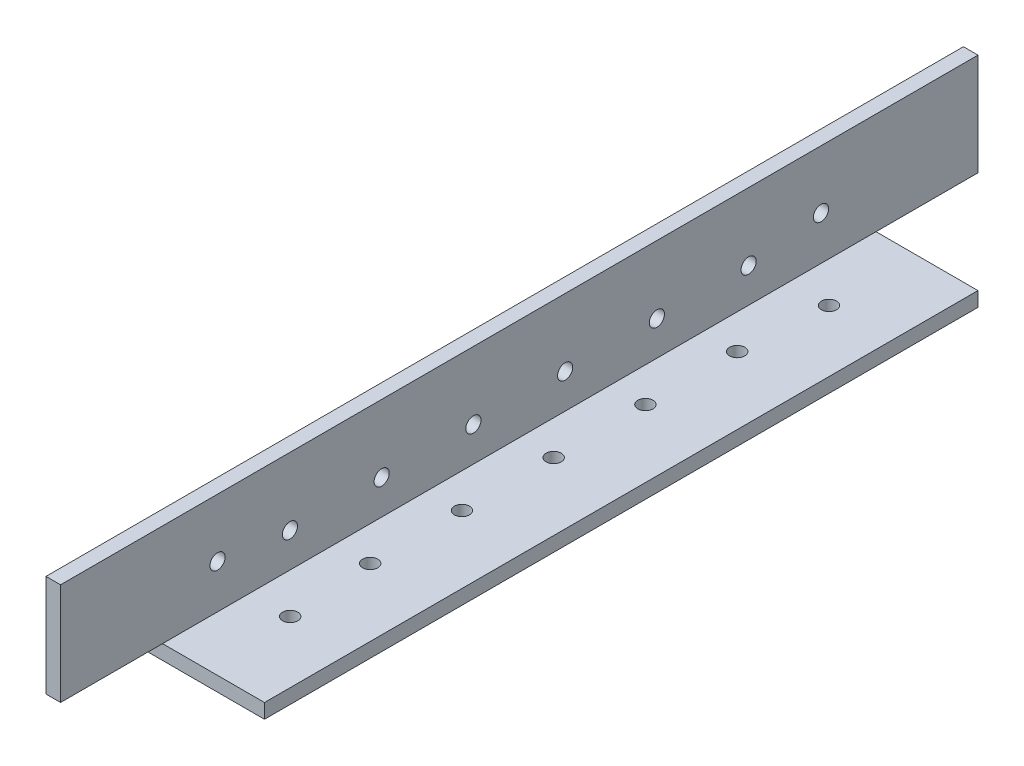
SolidWorks part; units mm, degrees
ref_plane "Front Plane" through (0, 0, 0) normal (0, 0, 1) x (1, 0, 0)
ref_plane "Top Plane" through (0, 0, 0) normal (0, 1, 0) x (1, 0, 0)
ref_plane "Right Plane" through (0, 0, 0) normal (1, 0, 0) x (0, 0, -1)
sketch "Sketch1" plane through (0, 0, 0) normal (0, 0, 1) x (1, 0, 0)
  line L0 (0, 25.4) -> (0, 0) construction
  line L1 (0, 0) -> (25.4, 0) construction
  line L2 (25.4, 0) -> (25.4, 3.175) construction
  line L3 (25.4, 3.175) -> (3.175, 3.175) construction
  line L4 (3.175, 3.175) -> (3.175, 25.4) construction
  line L6 (3.175, 25.4) -> (0, 25.4) construction
  arc A0 (3.175, 3.5814) -> (3.5814, 3.175) centre (3.5814, 3.5814) ccw construction
  point P4 (0, 0)
  dimension "Inside Corner Radius" = 0.4064
  dimension "Outside Height" = 25.4
  dimension "Inside Height" = 22.225
  dimension "Outside Width" = 25.4
  dimension "Inside Width" = 22.225
  dimension "Wall Thickness" = 3.175
  dimension "Shape" = 90
sketch "Sketch2" plane through (0, 0, 0) normal (1, 0, 0) x (0, 0, -1)
  line L0 (1219.2, 0) -> (-1219.2, 0) construction
  line L1 (-1219.2, 25.4) -> (-1219.2, 0) construction
  line L2 (1219.2, 25.4) -> (1219.2, 0) construction
  point P0 (-1189.99, 0)
  point P4 (0, 0)
  point P6 (1189.99, 0)
  dimension "D1" = 29.21
  dimension "D2" = 29.21
  dimension "D3" = 25.4
  dimension "Length" = 2438.4
sketch "Sketch3" plane through (0, 0, 0) normal (0, 0, 1) x (1, 0, 0)
  line L0 (3.175, 25.4) -> (0, 25.4)
  line L1 (0, 25.4) -> (0, 0)
  line L2 (0, 0) -> (25.4, 0)
  line L3 (25.4, 0) -> (25.4, 3.175)
  line L4 (25.4, 3.175) -> (3.175, 3.175)
  line L5 (3.175, 3.175) -> (3.175, 25.4)
extrude "Boss-Extrude1" add sketch "Sketch3" along normal mid plane 2438.4
fillet "Fillet1" radius 0.4064 1 edges at (3.175, 3.175, 0)
sketch "Sketch4" plane through (0, 0, 0) normal (-1, 0, 0) x (0, 0, 1)
  line L0 (1219.2, 25.4) -> (1219.2, 0) construction
  line L1 (-1219.2, 25.4) -> (1019.2, 25.4)
  line L2 (-1219.2, 25.4) -> (-1219.2, -77.8785)
  line L3 (-1219.2, -77.8785) -> (1019.2, -77.8785)
  line L4 (1019.2, 25.4) -> (1019.2, -77.8785)
  dimension "D1" = 200
extrude "Cut-Extrude1" cut sketch "Sketch4" against normal blind 60
sketch "Sketch5" plane through (0, 0, 0) normal (0, -1, 0) x (1, 0, 0)
  line L0 (0, 1219.2) -> (0, 1019.2) construction
  line L1 (25.4, 1019.2) -> (0, 1019.2)
  line L2 (25.4, 1019.2) -> (25.4, 1041.43)
  line L3 (25.4, 1041.43) -> (0, 1041.43)
  line L4 (0, 1019.2) -> (0, 1041.43)
  dimension "D1" = 22.23
extrude "Cut-Extrude2" cut sketch "Sketch5" against normal up to surface (3.175 mm away) up to face at (14.4907, 3.175, 1119.2)
sketch "Sketch6" plane through (0, 0, 0) normal (0, -1, 0) x (1, 0, 0)
  line L0 (0, 1219.2) -> (0, 1041.43) construction
  line L1 (25.4, 1219.2) -> (0, 1219.2)
  line L2 (25.4, 1219.2) -> (25.4, 1196.97)
  line L3 (25.4, 1196.97) -> (0, 1196.97)
  line L4 (0, 1219.2) -> (0, 1196.97)
  dimension "D1" = 22.23
extrude "Cut-Extrude3" cut sketch "Sketch6" against normal up to surface (3.175 mm away) up to face at (14.4907, 3.175, 1130.315)
sketch "Sketch7" plane through (0, 0, 1019.2) normal (0, 0, -1) x (-1, 0, 0)
  line L0 (-3.175, 3.5814) -> (-3.175, 25.4) construction
  line L1 (-3.175, 4.2) -> (-4.4439, 4.2)
  line L2 (-3.175, 4.2) -> (-3.175, 3.175)
  line L3 (-3.175, 3.175) -> (-4.4439, 3.175)
  line L4 (-4.4439, 4.2) -> (-4.4439, 3.175)
  line L5 (-3.5814, 3.175) -> (-25.4, 3.175) construction
extrude "Cut-Extrude4" cut sketch "Sketch7" against normal blind 220
sketch "Sketch9" plane through (3.175, 0, 0) normal (1, 0, 0) x (0, 0, -1)
  line L0 (-1219.2, 3.175) -> (-1219.2, 25.4) construction
  line L1 (-1196.97, 3.175) -> (-1041.43, 3.175) construction
  line L2 (-1019.2, 3.175) -> (-1019.2, 25.4) construction
  circle A0 centre (-1169.2, 10.675) radius 1.65
  circle A1 centre (-1149.2, 10.675) radius 1.65
  circle A2 centre (-1129.2, 10.675) radius 1.65
  circle A3 centre (-1109.2, 10.675) radius 1.65
  circle A4 centre (-1089.2, 10.675) radius 1.65
  circle A5 centre (-1069.2, 10.675) radius 1.65
  dimension "D1" = 50
  dimension "D2" = 7.5
  dimension "D3" = 3.3
  dimension "D5" = 50
  dimension "D4" = 6
extrude "Cut-Extrude5" cut sketch "Sketch9" against normal blind 20
sketch "Sketch10" plane through (0, 3.175, 0) normal (0, 1, 0) x (1, 0, 0)
  line L0 (600, -1019.2) -> (0, -1019.2) construction
  line L1 (3.175, -1196.97) -> (3.175, -1041.43) construction
  circle A0 centre (10.675, -1079.2) radius 1.65
  circle A1 centre (10.675, -1099.2) radius 1.65
  circle A2 centre (10.675, -1119.2) radius 1.65
  circle A3 centre (10.675, -1139.2) radius 1.65
  circle A4 centre (10.675, -1159.2) radius 1.65
  dimension "D1" = 60
  dimension "D2" = 7.5
  dimension "D3" = 3.3
  dimension "D5" = 20
  dimension "D4" = 5
extrude "Cut-Extrude6" cut sketch "Sketch10" against normal blind 20
sketch "Sketch11" plane through (3.175, 0, 0) normal (1, 0, 0) x (0, 0, -1)
  circle A0 centre (-1053.4257, 12.7) radius 1.65
  circle A1 centre (-1184.9793, 12.7) radius 1.65
  dimension "D1" = 3.3
extrude "Cut-Extrude7" cut sketch "Sketch11" against normal blind 70
sketch "Sketch12" plane through (0, 3.175, 0) normal (0, 1, 0) x (1, 0, 0)
  circle A0 centre (11.9634, -1177.925) radius 1.65
  circle A1 centre (11.9634, -1060.48) radius 1.65
  dimension "D1" = 3.3
extrude "Cut-Extrude8" cut sketch "Sketch12" against normal blind 70
equation "\"D1@Boss-Extrude1\"=\"Length@Sketch2\""
equation "\"D1@Sketch2\" = \"Outside Width@Sketch1\" * 1.15"
equation "\"D2@Sketch2\"=\"D1@Sketch2\""
equation "\"D1@Fillet1\"=\"Inside Corner Radius@Sketch1\""
equation "\"D3@Sketch2\"=\"Outside Height@Sketch1\""
